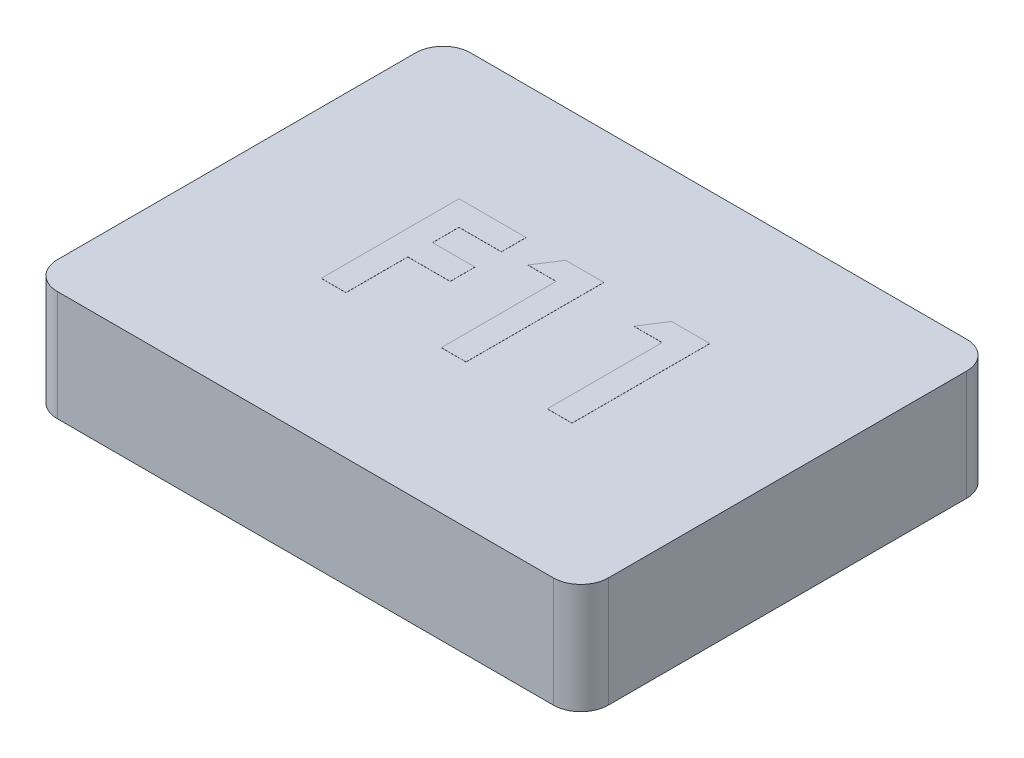
SolidWorks part; units mm, degrees
ref_plane "Front Plane" through (0, 0, 0) normal (0, 0, 1) x (1, 0, 0)
ref_plane "Top Plane" through (0, 0, 0) normal (0, 1, 0) x (1, 0, 0)
ref_plane "Right Plane" through (0, 0, 0) normal (1, 0, 0) x (0, 0, -1)
sketch "Sketch1" plane through (0, 0, 0) normal (0, 1, 0) x (1, 0, 0)
  line L0 (0, 0) -> (12.7, 0)
  line L1 (12.7, 0) -> (12.7, 9.525)
  line L2 (12.7, 9.525) -> (0, 9.525)
  line L3 (0, 9.525) -> (0, 0)
  dimension "D1" = 12.7
  dimension "D2" = 9.525
extrude "Boss-Extrude1" add sketch "Sketch1" along normal blind 2.54
fillet "Fillet1" radius 0.635 4 edges at (0, 1.27, -9.525) (12.7, 1.27, -9.525) (12.7, 1.27, 0) (0, 1.27, 0)
shell "Shell1" thickness 0.635 removed face at (6.35, 0, -4.7625)
sketch "Sketch2" plane through (0, 1.905, 0) normal (0, -1, 0) x (-1, 0, 0)
  line L0 (-0.635, 4.7625) -> (-12.065, 4.7625) construction
  line L1 (-0.635, 8.89) -> (-0.635, 0.635) construction
  line L2 (-12.065, 0.635) -> (-12.065, 8.89) construction
  line L3 (-6.35, 0.635) -> (-6.35, 8.89) construction
  line L4 (-0.635, 0.635) -> (-12.065, 0.635) construction
  line L5 (-12.065, 8.89) -> (-0.635, 8.89) construction
  circle A0 centre (-6.35, 4.7625) radius 2.54
  dimension "D1" = 5.08
extrude "Boss-Extrude2" add sketch "Sketch2" along normal up to surface (1.905 mm away) up to face at (6.35, 0, -4.7625)
sketch "Sketch3" plane through (0, 2.54, 0) normal (0, 1, 0) x (1, 0, 0)
  line L0 (0.635, 0) -> (12.065, 0) construction
  line L1 (0, 8.89) -> (0, 0.635) construction
  text T0 "<b>F11</b>"
  dimension "D1" = 3.302
  dimension "D2" = 3.048
extrude "Boss-Extrude3" add sketch "Sketch3" along normal blind 0.0025
